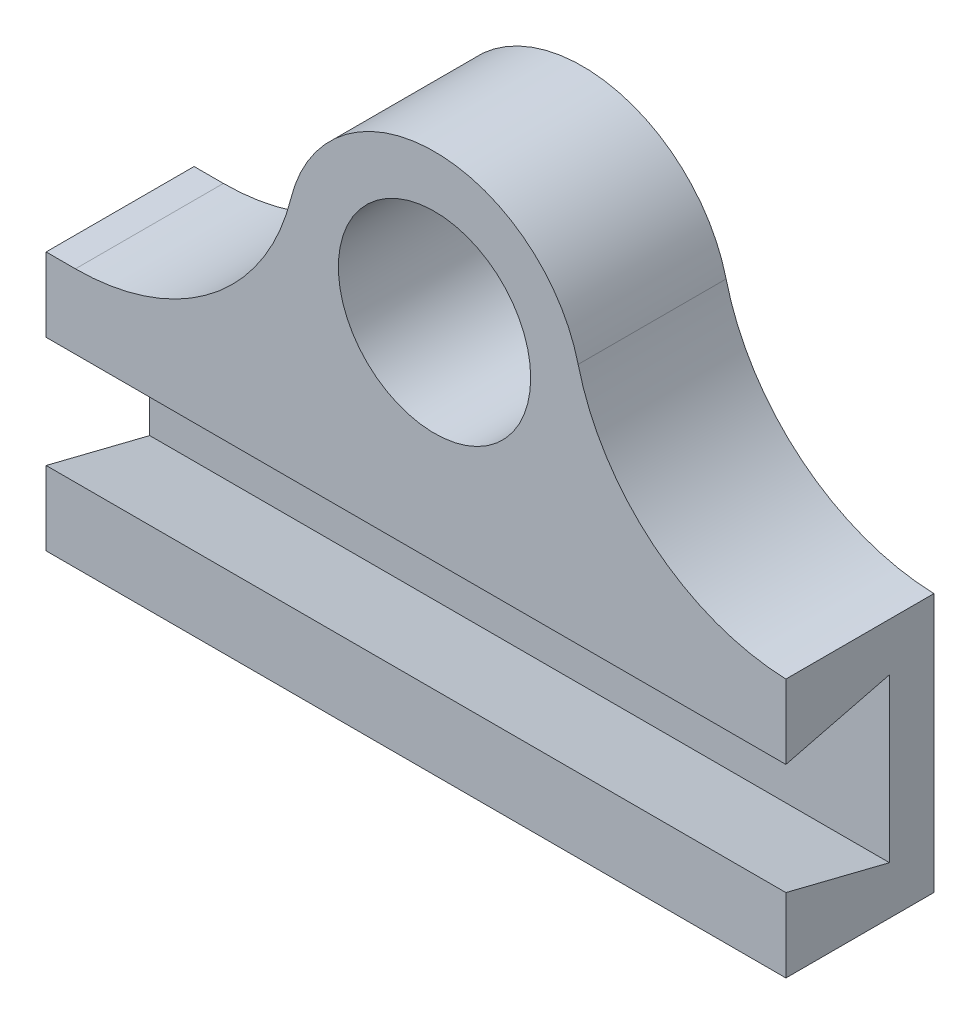
SolidWorks part; units mm, degrees
ref_plane "Plan de face" through (0, 0, 0) normal (0, 0, 1) x (1, 0, 0)
ref_plane "Plan de dessus" through (0, 0, 0) normal (0, 1, 0) x (1, 0, 0)
ref_plane "Plan de droite" through (0, 0, 0) normal (1, 0, 0) x (0, 0, -1)
sketch "Esquisse1" plane through (0, 0, 0) normal (0, 0, 1) x (1, 0, 0)
  line L0 (-61.0134, -26.0826) -> (-61.0134, -22.5826)
  line L1 (-61.0134, -26.0826) -> (-71.0134, -26.0826)
  line L2 (-61.0134, -22.5826) -> (-71.0134, -22.5826)
  line L3 (-71.0134, -26.0826) -> (-71.0134, -22.5826)
  line L4 (-68.1134, -31.0864) -> (-65.9134, -31.0864) construction
  line L7 (-67.0134, -26.0826) -> (-67.0134, -31.0864) construction
  point P15 (-67.0134, -31.0864)
  dimension "D1" = 4
  dimension "D2" = 6
  dimension "D3" = 3.5
extrude "Boss.-Extru.1" add sketch "Esquisse1" along normal blind 2
sketch "Esquisse2" plane through (-71.0134, 0, 0) normal (-1, 0, 0) x (0, 0, 1)
  line L0 (2, -25.0826) -> (2, -23.5826)
  line L1 (2, -22.5826) -> (2, -26.0826) construction
  line L2 (2, -25.0826) -> (0.6, -25.4326)
  line L3 (0.6, -25.4326) -> (0.6, -23.2326)
  line L4 (0.6, -23.2326) -> (2, -23.5826)
  line L5 (2, -24.3326) -> (0.6, -24.3326) construction
  point P4 (2, -24.3326)
  point P5 (2, -24.3326)
  dimension "D1" = 1.4
  dimension "D2" = 1.5
  dimension "D3" = 2.2
extrude "Enlèv. mat.-Extru.1" cut sketch "Esquisse2" against normal through all
sketch "Esquisse3" plane through (0, -26.0826, 0) normal (0, -1, 0) x (1, 0, 0)
  line L0 (-66.5134, 0) -> (-66.2134, -1.1)
  line L1 (-71.0134, 0) -> (-61.0134, 0) construction
  line L2 (-66.2134, -1.1) -> (-67.8134, -1.1)
  line L3 (-67.8134, -1.1) -> (-67.5134, 0)
  line L4 (-67.5134, 0) -> (-66.5134, 0)
  line L5 (-67.0134, -1.1) -> (-67.0134, 0) construction
  line L7 (-67.0134, -1.1) -> (-67.0134, -1.5) construction
  line L8 (-68.1134, -1.5) -> (-65.9134, -1.5) construction
  point P10 (-67.0134, -1.5)
  dimension "D1" = 1
  dimension "D2" = 1.1
  dimension "D3" = 1.6
extrude "Boss.-Extru.2" add sketch "Esquisse3" against normal blind 3.5
sketch "Esquisse4" plane through (0, 0, 2) normal (0, 0, 1) x (1, 0, 0)
  line L0 (-61.0134, -22.5826) -> (-71.0134, -22.5826) construction
  line L1 (-64.8916, -22.5826) -> (-66.6352, -22.5826)
  line L2 (-65.7634, -22.5826) -> (-65.7634, -20.7826) construction
  line L3 (-65.2634, -31.0864) -> (-65.2634, -30.8172) construction
  arc A0 (-64.8916, -22.5826) -> (-66.6352, -22.5826) centre (-65.7634, -20.7826) ccw
  dimension "D1" = 2
  dimension "D2" = 0.5
  dimension "D3" = 1.8
extrude "Boss.-Extru.3" add sketch "Esquisse4" against normal blind 2
sketch "Esquisse5" plane through (0, 0, 2) normal (0, 0, 1) x (1, 0, 0)
  circle A0 centre (-65.7634, -20.7826) radius 1.3
  dimension "D1" = 2.6
extrude "Enlèv. mat.-Extru.2" cut sketch "Esquisse5" against normal up to next
fillet "Congé1" radius 3 2 edges at (-66.6352, -22.5826, 1) (-64.8916, -22.5826, 1)
ref_plane "Plan1" through (-67.0134, 0, 0) normal (-1, 0, 0) x (0, 0, 1)
ref_plane "Plan2" through (0, -24.3326, 0) normal (0, -1, 0) x (-1, 0, 0)
